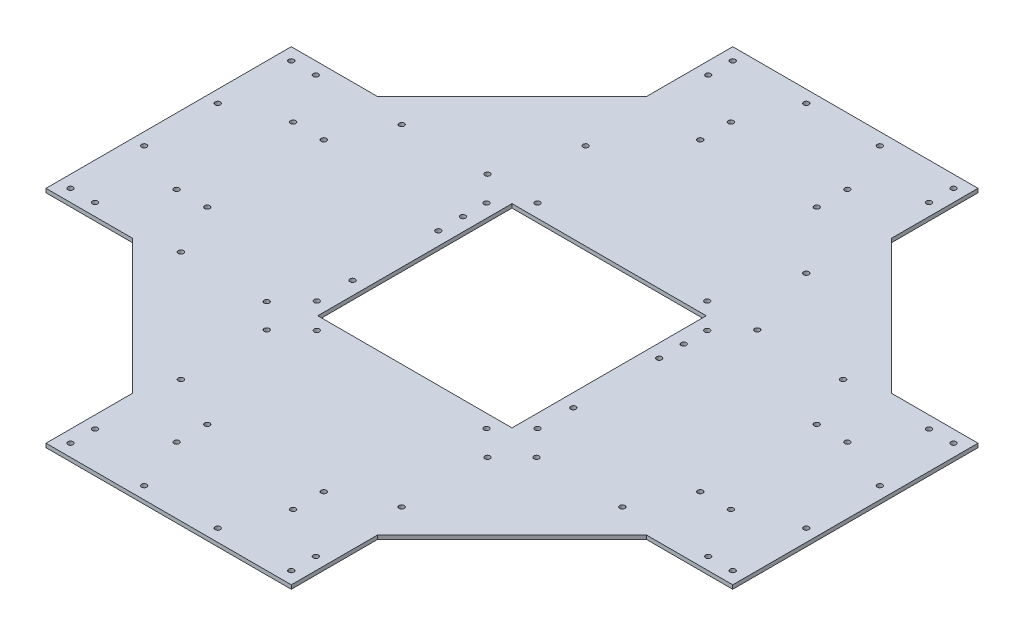
SolidWorks part; units mm, degrees
ref_plane "Front Plane" through (0, 0, 0) normal (0, 0, 1) x (1, 0, 0)
ref_plane "Top Plane" through (0, 0, 0) normal (0, 1, 0) x (1, 0, 0)
ref_plane "Right Plane" through (0, 0, 0) normal (1, 0, 0) x (0, 0, -1)
sketch "Sketch1" plane through (0, 0, 0) normal (0, 1, 0) x (1, 0, 0)
  line L0 (0, -280) -> (100, -280)
  line L1 (100, -280) -> (100, -209.6016)
  line L2 (280, -100) -> (209.6016, -100)
  line L3 (0, 0) -> (0, -280) construction
  line L4 (280, 0) -> (280, -100)
  line L5 (-280, 280) -> (280, 280) construction
  line L6 (-280, 280) -> (-280, -280) construction
  line L7 (-280, -280) -> (280, -280) construction
  line L8 (280, 280) -> (280, -280) construction
  line L9 (-280, 280) -> (280, -280) construction
  line L10 (-280, -280) -> (280, 280) construction
  line L11 (100, -209.6016) -> (209.6016, -100)
  line L12 (-280, 0) -> (-280, -100)
  line L13 (-280, -100) -> (-209.6016, -100)
  line L14 (-209.6016, -100) -> (-100, -209.6016)
  line L15 (-100, -280) -> (-100, -209.6016)
  line L16 (0, -280) -> (-100, -280)
  line L17 (0, 280) -> (-100, 280)
  line L18 (-100, 280) -> (-100, 209.6016)
  line L19 (-100, 209.6016) -> (-209.6016, 100)
  line L20 (-280, 100) -> (-209.6016, 100)
  line L21 (-280, 0) -> (-280, 100)
  line L22 (280, 0) -> (280, 100)
  line L23 (280, 100) -> (209.6016, 100)
  line L24 (209.6016, 100) -> (100, 209.6016)
  line L25 (100, 280) -> (100, 209.6016)
  line L26 (0, 280) -> (100, 280)
  line L27 (111.5258, -219.2889) -> (219.2889, -111.5258) construction
  line L28 (219.2889, -111.5258) -> (247.5732, -139.8101) construction
  line L29 (247.5732, -139.8101) -> (139.8101, -247.5732) construction
  line L30 (139.8101, -247.5732) -> (111.5258, -219.2889) construction
  line L31 (-100, -270) -> (100, -270) construction
  line L32 (-90, -280) -> (-90, 280) construction
  line L37 (-70, -70) -> (70, 70) construction
  line L38 (-70, 70) -> (70, -70) construction
  line L39 (-100, -260) -> (100, -260) construction
  line L40 (-280, 40) -> (280, 40) construction
  line L41 (0, 280) -> (0, 0) construction
  line L42 (-280, -90) -> (280, -90) construction
  line L43 (-260, -100) -> (-260, 100) construction
  line L44 (0, 0) -> (-280, 0) construction
  arc A0 (100, -280) -> (280, -100) centre (100, -100) ccw construction
  circle A1 centre (-47.5, -201) radius 2.125
  circle A2 centre (-47.5, -226) radius 2.125
  circle A3 centre (47.5, -226) radius 2.125
  circle A4 centre (47.5, -201) radius 2.125
  circle A5 centre (-201, 47.5) radius 2.125
  circle A6 centre (-226, 47.5) radius 2.125
  circle A7 centre (-201, -47.5) radius 2.125
  circle A8 centre (-226, -47.5) radius 2.125
  circle A9 centre (47.5, 201) radius 2.125
  circle A10 centre (47.5, 226) radius 2.125
  circle A11 centre (-47.5, 201) radius 2.125
  circle A12 centre (-47.5, 226) radius 2.125
  circle A13 centre (201, -47.5) radius 2.125
  circle A14 centre (226, -47.5) radius 2.125
  circle A15 centre (201, 47.5) radius 2.125
  circle A16 centre (226, 47.5) radius 2.125
  circle A17 centre (-90, -270) radius 2.125
  circle A18 centre (-30, -270) radius 2.125
  circle A19 centre (30, -270) radius 2.125
  circle A20 centre (90, -270) radius 2.125
  circle A21 centre (-270, 90) radius 2.125
  circle A22 centre (-270, 30) radius 2.125
  circle A23 centre (-270, -30) radius 2.125
  circle A24 centre (-270, -90) radius 2.125
  circle A25 centre (90, 270) radius 2.125
  circle A26 centre (30, 270) radius 2.125
  circle A27 centre (-30, 270) radius 2.125
  circle A28 centre (-90, 270) radius 2.125
  circle A29 centre (270, -90) radius 2.125
  circle A30 centre (270, -30) radius 2.125
  circle A31 centre (270, 30) radius 2.125
  circle A32 centre (270, 90) radius 2.125
  circle A33 centre (-90, -250) radius 2.125
  circle A34 centre (-90, -180) radius 2.125
  circle A35 centre (-90, -110) radius 2.125
  circle A36 centre (-90, -40) radius 2.125
  circle A37 centre (-90, 30) radius 2.125
  circle A38 centre (-90, 50) radius 2.125
  circle A39 centre (-90, 100) radius 2.125 construction
  circle A40 centre (-90, 150) radius 2.125
  circle A41 centre (-90, 200) radius 2.125 construction
  circle A42 centre (-90, 250) radius 2.125
  circle A43 centre (90, -250) radius 2.125
  circle A44 centre (90, -180) radius 2.125
  circle A45 centre (90, -110) radius 2.125
  circle A46 centre (90, -40) radius 2.125
  circle A47 centre (90, 30) radius 2.125
  circle A48 centre (90, 50) radius 2.125
  circle A49 centre (90, 100) radius 2.125 construction
  circle A50 centre (90, 150) radius 2.125
  circle A51 centre (90, 200) radius 2.125 construction
  circle A52 centre (90, 250) radius 2.125
  circle A53 centre (-250, -90) radius 2.125
  circle A54 centre (-180, -90) radius 2.125
  circle A55 centre (-110, -90) radius 2.125
  circle A56 centre (-110, 90) radius 2.125
  circle A57 centre (-180, 90) radius 2.125
  circle A58 centre (-250, 90) radius 2.125
  circle A59 centre (110, -90) radius 2.125
  circle A60 centre (180, -90) radius 2.125
  circle A61 centre (250, -90) radius 2.125
  circle A62 centre (110, 90) radius 2.125
  circle A63 centre (180, 90) radius 2.125
  circle A64 centre (250, 90) radius 2.125
  point P33 (0, 0)
  point P68 (0, 0)
  point P107 (0, 0)
  dimension "D10" = 25
  dimension "4.25" = 4.25
  dimension "D11" = 4.25
  dimension "D16" = 4.25
  dimension "D24" = 4.25
  dimension "D28" = 4.25
  dimension "D32" = 4.25
  dimension "D1" = 560
  dimension "D2" = 90
  dimension "D3" = 280
  dimension "D4" = 4
  dimension "D5" = 100
  dimension "D6" = 155
  dimension "D7" = 152.4
  dimension "D8" = 15
  dimension "D9" = 40
  dimension "D12" = 47.5
  dimension "D13" = 54
  dimension "D15" = 10
  dimension "D17" = 10
  dimension "D18" = 76.2
  dimension "D23" = 10
  dimension "D25" = 10
  dimension "D26" = 300
  dimension "D29" = 10
  dimension "D31" = 20
  dimension "D33" = 10
  dimension "D21" = 4
  dimension "D27" = 5
  dimension "D30" = 5
  dimension "D34" = 3
  dimension "D14" = 4
  dimension "D22" = 4
extrude "Boss-Extrude1" add sketch "Sketch1" along normal blind 3.175 contours L26 L17 L18 L19 L20 L21 L12 L13 L14 L15 L16 L0 L1 L11 L2 L4 L22 L23 L24 L25 region at (0, 0, -0.0137)
sketch "Sketch2" plane through (0, 3.175, 0) normal (0, 1, 0) x (1, 0, 0)
  line L0 (-90, -280) -> (-90, 280) construction
  line L1 (-79.2, -79.2) -> (79.2, -79.2)
  line L2 (-79.2, -79.2) -> (-79.2, 79.2)
  line L3 (-79.2, 79.2) -> (79.2, 79.2)
  line L4 (79.2, -79.2) -> (79.2, 79.2)
  line L5 (-79.2, -79.2) -> (79.2, 79.2) construction
  line L6 (-79.2, 79.2) -> (79.2, -79.2) construction
  line L7 (-90, -280) -> (-90, 280) construction
  line L8 (-79.2, 0) -> (79.2, 0) construction
  line L9 (0, 79.2) -> (0, -79.2) construction
  line L10 (-110, 90) -> (110, 90) construction
  circle A0 centre (-90, 50) radius 2.125 construction
  circle A1 centre (-90, 69.2) radius 2.125
  circle A2 centre (-90, -69.2) radius 2.125
  circle A3 centre (90, -69.2) radius 2.125
  circle A4 centre (90, 69.2) radius 2.125
  circle A5 centre (-69.2, 90) radius 2.125
  circle A6 centre (69.2, 90) radius 2.125
  circle A7 centre (69.2, -90) radius 2.125
  circle A8 centre (-69.2, -90) radius 2.125
  point P0 (0, 0)
  dimension "D3" = 4.25
  dimension "D5" = 4.25
  dimension "D1" = 10.8
  dimension "D2" = 158.4
  dimension "D4" = 10
  dimension "D6" = 10
extrude "Cut-Extrude1" cut sketch "Sketch2" against normal through all
